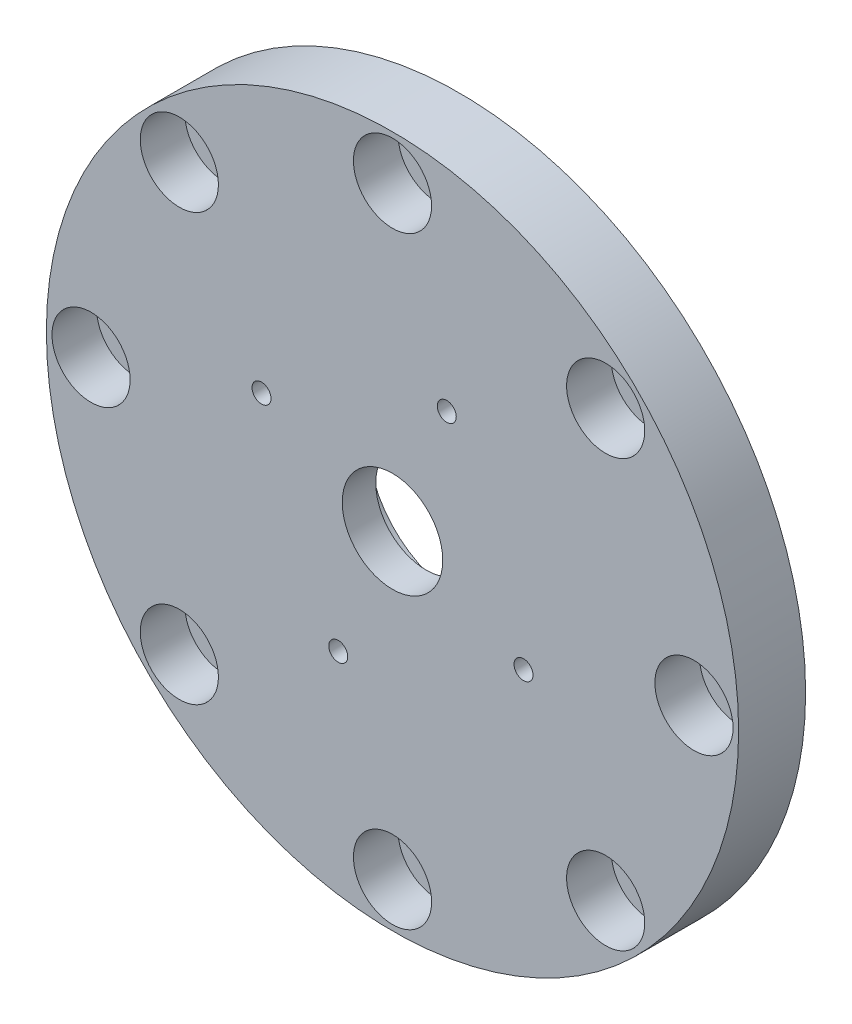
SolidWorks part; units mm, degrees
ref_plane "Front Plane" through (0, 0, 0) normal (0, 0, 1) x (1, 0, 0)
ref_plane "Top Plane" through (0, 0, 0) normal (0, 1, 0) x (1, 0, 0)
ref_plane "Right Plane" through (0, 0, 0) normal (1, 0, 0) x (0, 0, -1)
sketch "Sketch1" plane through (0, 0, 0) normal (0, 0, 1) x (1, 0, 0)
  line L11 (0, 0) -> (4.8601, 11.7333) construction
  line L14 (-11.7333, 4.8601) -> (11.7333, -4.8601) construction
  line L17 (0, 0) -> (-27, 0) construction
  circle A2 centre (0, 0) radius 4.5
  circle A3 centre (0, 0) radius 12.7 construction
  circle A11 centre (4.8601, 11.7333) radius 0.85
  circle A12 centre (11.7333, -4.8601) radius 0.85
  circle A13 centre (-4.8601, -11.7333) radius 0.85
  circle A14 centre (-11.7333, 4.8601) radius 0.85
  circle A33 centre (0, 0) radius 24 construction
  circle A34 centre (0, 0) radius 31
  circle A35 centre (-27, 0) radius 1.55
  circle A36 centre (-19.0919, 19.0919) radius 1.55
  circle A37 centre (0, 27) radius 1.55
  circle A38 centre (19.0919, 19.0919) radius 1.55
  circle A39 centre (27, 0) radius 1.55
  circle A40 centre (19.0919, -19.0919) radius 1.55
  circle A41 centre (0, -27) radius 1.55
  circle A42 centre (-19.0919, -19.0919) radius 1.55
  point P7 (0, 0)
  point P10 (0, 0)
  point P12 (0, 0)
  point P16 (0, 0)
  point P17 (0, 0)
  point P20 (0, 0)
  point P30 (0, 0)
  point P39 (0, 0)
  point P40 (0, 0)
  point P47 (0, 0)
  point P64 (0, 0)
  dimension "D1" = 4
extrude "Boss-Extrude2" add sketch "Sketch1" along normal blind 6
sketch "Sketch5" plane through (0, 0, 0) normal (0, 0, -1) x (-1, 0, 0)
  circle A0 centre (0, 0) radius 8.2
extrude "Cut-Extrude3" cut sketch "Sketch5" against normal blind 3
sketch "Sketch6" plane through (0, 0, 6) normal (0, 0, 1) x (1, 0, 0)
  circle A7 centre (0, 27) radius 3.5
  circle A8 centre (19.0919, 19.0919) radius 3.5
  circle A9 centre (27, 0) radius 3.5
  circle A10 centre (19.0919, -19.0919) radius 3.5
  circle A11 centre (0, -27) radius 3.5
  circle A12 centre (-19.0919, -19.0919) radius 3.5
  circle A13 centre (-27, 0) radius 3.5
  circle A14 centre (-19.0919, 19.0919) radius 3.5
  point P11 (-3.75, 3.75)
  point P29 (0, 0)
  point P31 (0, 0)
  dimension "D2" = 8
extrude "Cut-Extrude4" cut sketch "Sketch6" against normal blind 4
sketch "Sketch7" plane through (0, 0, 0) normal (0, 0, -1) x (-1, 0, 0)
  circle A1 centre (-4.8601, 11.7333) radius 2.2
  circle A2 centre (11.7333, 4.8601) radius 2.2
  circle A3 centre (4.8601, -11.7333) radius 2.2
  circle A4 centre (-11.7333, -4.8601) radius 2.2
  point P12 (0, 0)
  dimension "D1" = 4
extrude "Cut-Extrude5" cut sketch "Sketch7" against normal blind 2
